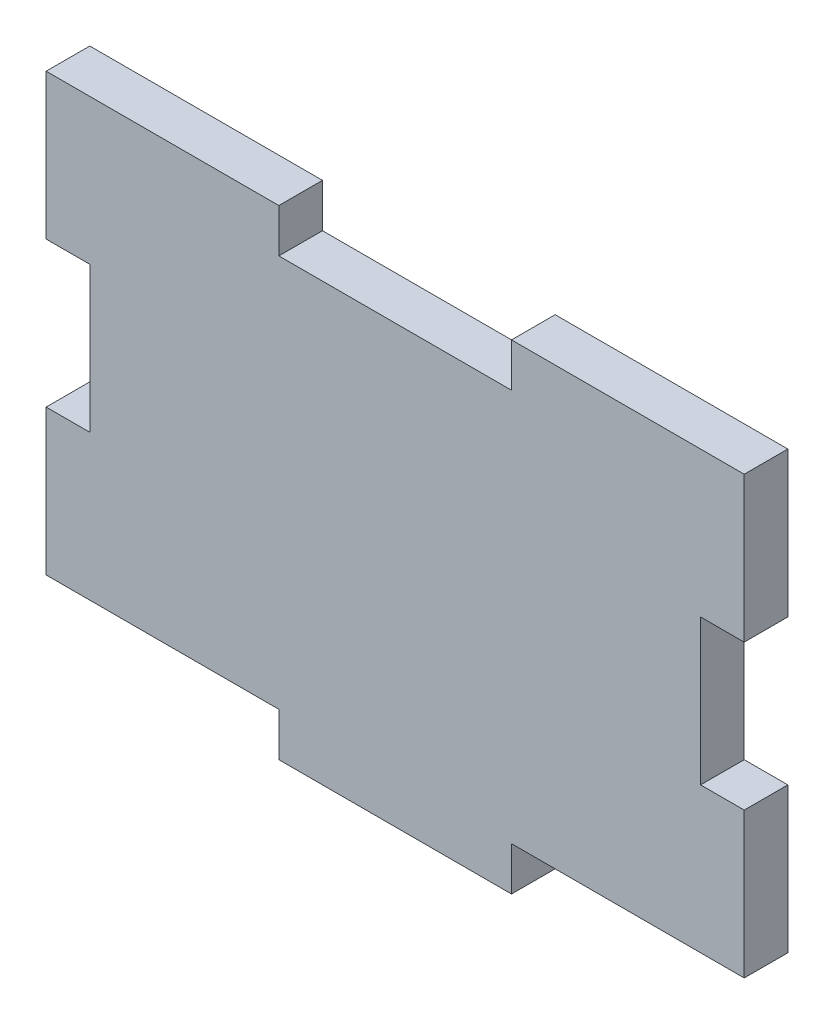
SolidWorks part; units mm, degrees
ref_plane "Alzado" through (0, 0, 0) normal (0, 0, 1) x (1, 0, 0)
ref_plane "Planta" through (0, 0, 0) normal (0, 1, 0) x (1, 0, 0)
ref_plane "Vista lateral" through (0, 0, 0) normal (1, 0, 0) x (0, 0, -1)
sketch "Croquis1" plane through (0, 0, 0) normal (0, 0, 1) x (1, 0, 0)
  line L0 (40, 55) -> (40, 48.9607) construction
  line L1 (0, 0) -> (80, 0)
  line L2 (0, 0) -> (0, 55)
  line L3 (0, 55) -> (80, 55)
  line L4 (80, 0) -> (80, 55)
  line L5 (0, 55) -> (5, 55)
  line L6 (0, 55) -> (0, 0)
  line L7 (0, 0) -> (5, 0)
  line L8 (5, 55) -> (5, 0)
  line L9 (0, 0) -> (80, 0)
  line L10 (0, 0) -> (0, 5)
  line L11 (0, 5) -> (80, 5)
  line L12 (80, 0) -> (80, 5)
  line L13 (26.6667, 5) -> (26.6667, 0)
  line L14 (53.3333, 5) -> (53.3333, 0)
  line L15 (0, 38.3333) -> (5, 38.3333)
  line L16 (0, 21.6667) -> (5, 21.6667)
  line L17 (75, 55) -> (75, 0)
  line L18 (80, 21.6667) -> (75, 21.6667)
  line L19 (80, 38.3333) -> (75, 38.3333)
  point P19 (53.3333, 2.5)
  dimension "D1" = 80
  dimension "D2" = 55
  dimension "D3" = 5
  dimension "D4" = 5
  dimension "D5" = 16.6667
  dimension "D6" = 16.6667
  dimension "D7" = 26.6667
  dimension "D8" = 26.6667
extrude "Saliente-Extruir1" add sketch "Croquis1" along normal blind 5 contours L2 L15 L8 L3 | L16 L6 L11 L8 | L17 L3 L8 L11 | L19 L4 L3 L17 | L4 L18 L17 L11 | L14 L11 L13 L9 region at (2.5, 13.3333, 0) region at (40, 2.5, 0) region at (40, 30, 0) region at (2.5, 46.6667, 0) region at (77.5, 13.3333, 0) region at (77.5, 46.6667, 0)
sketch "Croquis2" plane through (0, 0, 5) normal (0, 0, 1) x (1, 0, 0)
  line L0 (0, 55) -> (80, 55) construction
  line L1 (53.3333, 55) -> (26.6667, 55)
  line L2 (53.3333, 55) -> (53.3333, 50)
  line L3 (53.3333, 50) -> (26.6667, 50)
  line L4 (26.6667, 55) -> (26.6667, 50)
  line L6 (0, 38.3333) -> (0, 55) construction
  line L7 (80, 38.3333) -> (80, 55) construction
  dimension "D1" = 5
  dimension "D2" = 26.6667
  dimension "D3" = 26.6667
extrude "Cortar-Extruir1" cut sketch "Croquis2" against normal blind 10
sketch "Croquis3" plane through (0, 0, 5) normal (0, 0, 1) x (1, 0, 0)
  line L20 (53.3333, 55) -> (53.3333, 50)
  line L21 (53.3333, 50) -> (26.6667, 50)
  line L22 (26.6667, 50) -> (26.6667, 55)
  line L23 (26.6667, 55) -> (0, 55)
  line L24 (0, 55) -> (0, 38.3333)
  line L25 (0, 38.3333) -> (5, 38.3333)
  line L26 (5, 38.3333) -> (5, 21.6667)
  line L27 (5, 21.6667) -> (0, 21.6667)
  line L28 (0, 21.6667) -> (0, 5)
  line L29 (0, 5) -> (26.6667, 5)
  line L30 (26.6667, 5) -> (26.6667, 0)
  line L31 (26.6667, 0) -> (53.3333, 0)
  line L32 (53.3333, 0) -> (53.3333, 5)
  line L33 (53.3333, 5) -> (80, 5)
  line L34 (80, 5) -> (80, 21.6667)
  line L35 (80, 21.6667) -> (75, 21.6667)
  line L36 (75, 21.6667) -> (75, 38.3333)
  line L37 (75, 38.3333) -> (80, 38.3333)
  line L38 (80, 38.3333) -> (80, 55)
  line L39 (80, 55) -> (53.3333, 55)
  line L40 (53.3333, 55) -> (53.3333, 50)
  line L41 (53.3333, 50) -> (26.6667, 50)
  line L42 (26.6667, 50) -> (26.6667, 55)
  line L43 (26.6667, 55) -> (0, 55)
  line L44 (0, 55) -> (0, 38.3333)
  line L45 (0, 38.3333) -> (5, 38.3333)
  line L46 (5, 38.3333) -> (5, 21.6667)
  line L47 (5, 21.6667) -> (0, 21.6667)
  line L48 (0, 21.6667) -> (0, 5)
  line L49 (0, 5) -> (26.6667, 5)
  line L50 (26.6667, 5) -> (26.6667, 0)
  line L51 (26.6667, 0) -> (53.3333, 0)
  line L52 (53.3333, 0) -> (53.3333, 5)
  line L53 (53.3333, 5) -> (80, 5)
  line L54 (80, 5) -> (80, 21.6667)
  line L55 (80, 21.6667) -> (75, 21.6667)
  line L56 (75, 21.6667) -> (75, 38.3333)
  line L57 (75, 38.3333) -> (80, 38.3333)
  line L58 (80, 38.3333) -> (80, 55)
  line L59 (80, 55) -> (53.3333, 55)
  dimension "D1" = 0
